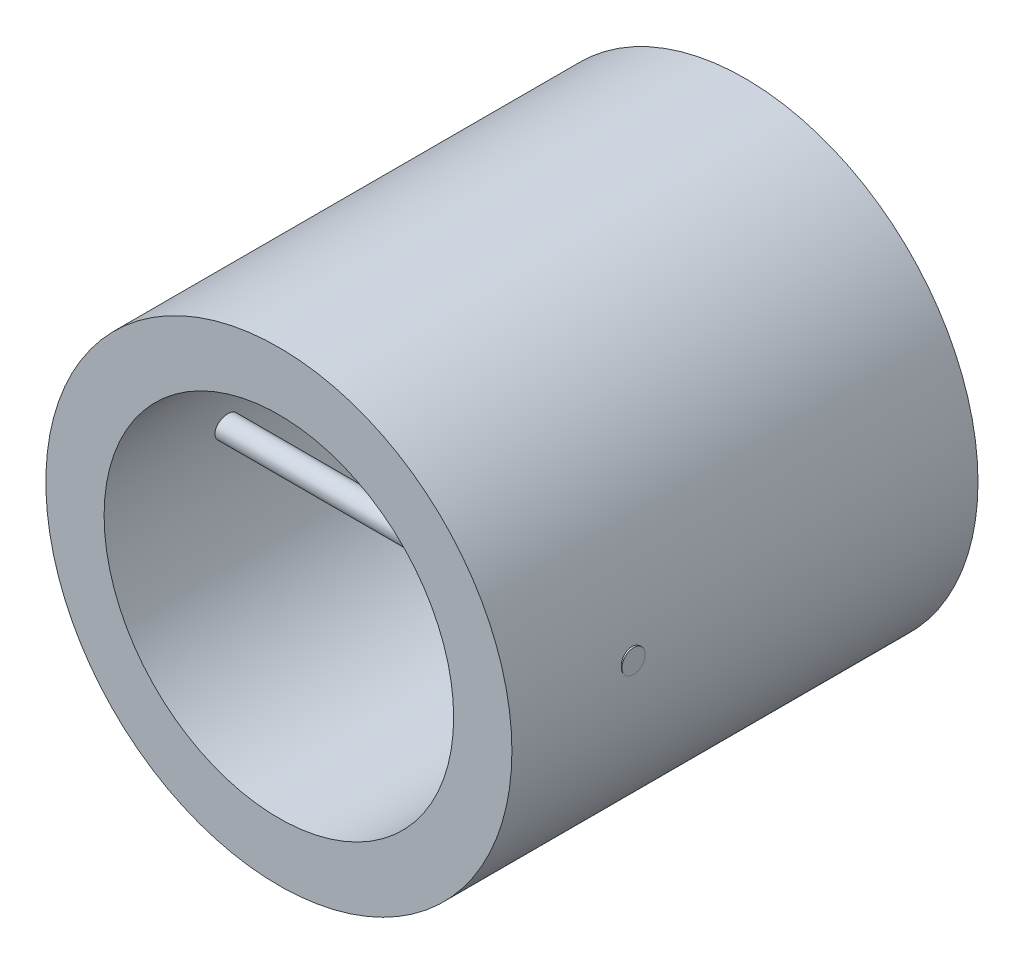
SolidWorks part; units mm, degrees
ref_plane "Front Plane" through (0, 0, 0) normal (0, 0, 1) x (1, 0, 0)
ref_plane "Top Plane" through (0, 0, 0) normal (0, 1, 0) x (1, 0, 0)
ref_plane "Right Plane" through (0, 0, 0) normal (1, 0, 0) x (0, 0, -1)
sketch "Sketch1" plane through (0, 0, 0) normal (0, 0, 1) x (1, 0, 0)
  circle A0 centre (0, 0) radius 15
  circle A1 centre (0, 0) radius 20
  dimension "D1" = 30
  dimension "D2" = 5
extrude "Boss-Extrude1" add sketch "Sketch1" along normal blind 20 and the other way blind 20
sketch "Sketch2" plane through (0, 0, 0) normal (1, 0, 0) x (0, 0, -1)
  circle A0 centre (-9.5589, 1.4612) radius 1
  dimension "D1" = 2
extrude "Boss-Extrude2" add sketch "Sketch2" along normal through all and the other way through all
